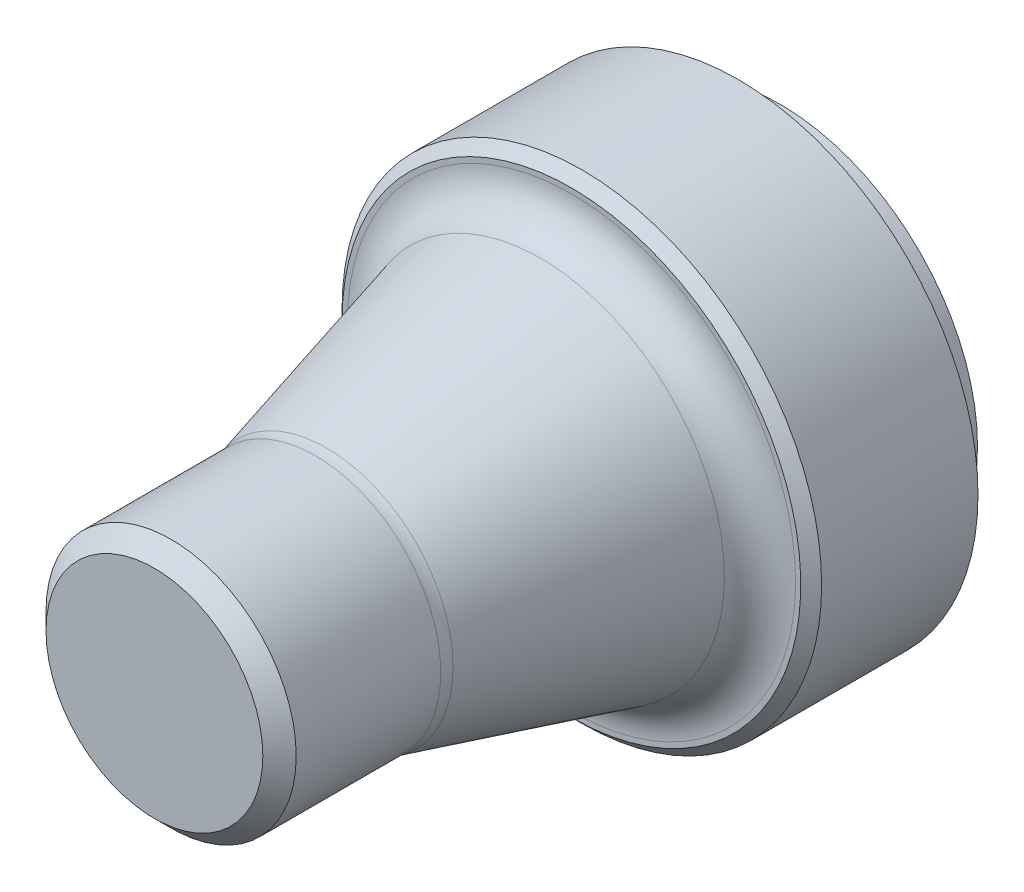
SolidWorks part; units mm, degrees
material "PET"
ref_plane "Front Plane" through (0, 0, 0) normal (0, 0, 1) x (1, 0, 0)
ref_plane "Top Plane" through (0, 0, 0) normal (0, 1, 0) x (1, 0, 0)
ref_plane "Right Plane" through (0, 0, 0) normal (1, 0, 0) x (0, 0, -1)
sketch "Sketch1" plane through (0, 0, 0) normal (0, 0, 1) x (1, 0, 0)
  circle A2 centre (0, 0) radius 30.0863
  circle A3 centre (0, 0) radius 30.0863
  dimension "D1" = 1.27
extrude "Boss-Extrude1" add sketch "Sketch1" against normal blind 6.35
sketch "Sketch2" plane through (0, 0, 0) normal (0, 0, 1) x (1, 0, 0)
  circle A0 centre (0, 0) radius 36.5125 construction
  circle A1 centre (0, 0) radius 36.5125
extrude "Boss-Extrude2" add sketch "Sketch2" along normal blind 25.4
sketch "Sketch3" plane through (0, 0, 25.4) normal (0, 0, 1) x (1, 0, 0)
  circle A0 centre (0, 0) radius 19.05
  dimension "D1" = 38.1
extrude "Boss-Extrude3" add sketch "Sketch3" along normal blind 38.1
draft "Draft1" type of draft neutral plane draft angle 15 faces to draft 1 face at (19.05, 0, 63.5) neutral plane through (0, 0, 63.5) neutral plane normal (0, 0, 1) parameters "D1"=15
sketch "Sketch4" plane through (0, 0, 63.5) normal (0, 0, 1) x (1, 0, 0)
  circle A1 centre (0, 0) radius 19.05
  circle A2 centre (0, 0) radius 19.05
  dimension "D1" = 0
extrude "Boss-Extrude4" add sketch "Sketch4" along normal blind 25.4
chamfer "Chamfer1" distance 2.54 angle 45 1 edges at (19.05, 0, 88.9)
fillet "Fillet1" radius 6.35 2 edges at (29.2589, 0, 25.4) (19.05, 0, 63.5)
chamfer "Chamfer2" distance 1.5875 angle 45 1 edges at (36.5125, 0, 25.4)
